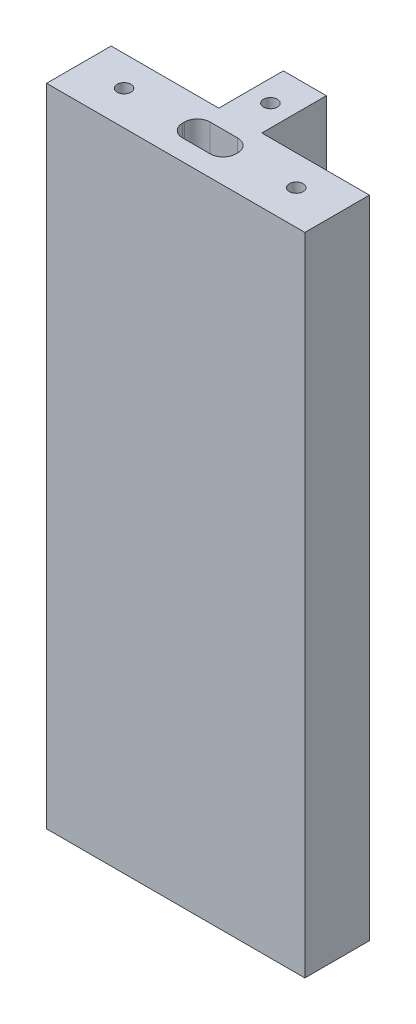
SolidWorks part; units mm, degrees
ref_plane "Front Plane" through (0, 0, 0) normal (0, 0, 1) x (1, 0, 0)
ref_plane "Top Plane" through (0, 0, 0) normal (0, 1, 0) x (1, 0, 0)
ref_plane "Right Plane" through (0, 0, 0) normal (1, 0, 0) x (0, 0, -1)
sketch "Sketch1" plane through (0, 0, 0) normal (0, 1, 0) x (1, 0, 0)
  line L0 (-15, 0) -> (15, 0)
  line L1 (15, 0) -> (15, 7.5)
  line L2 (15, 7.5) -> (2.5, 7.5)
  line L3 (2.5, 7.5) -> (2.5, 15)
  line L4 (2.5, 15) -> (-2.5, 15)
  line L5 (-2.5, 15) -> (-2.5, 7.5)
  line L6 (-2.5, 7.5) -> (-15, 7.5)
  line L7 (-15, 7.5) -> (-15, 0)
  dimension "D1" = 30
  dimension "D2" = 15
  dimension "D3" = 7.5
  dimension "D4" = 5
extrude "Boss-Extrude1" add sketch "Sketch1" along normal mid plane 75
sketch "Sketch2" plane through (0, -37.5, 0) normal (0, -1, 0) x (1, 0, 0)
  line L0 (-15, 0) -> (15, 0) construction
  line L1 (-3.1, -2.4) -> (3.1, -2.4)
  line L2 (-3.1, -2.4) -> (-3.1, -5.6)
  line L3 (-3.1, -5.6) -> (3.1, -5.6)
  line L4 (3.1, -2.4) -> (3.1, -5.6)
  point P4 (-3.1, -4)
  point P5 (0, -2.4)
  point P8 (0, 0)
  dimension "D1" = 4
  dimension "D2" = 3.2
  dimension "D3" = 6.2
extrude "Cut-Extrude1" cut sketch "Sketch2" against normal blind 6.2
fillet "Fillet1" radius 1.5 4 edges at (3.1, -34.4, -5.6) (3.1, -34.4, -2.4) (-3.1, -34.4, -5.6) (-3.1, -34.4, -2.4)
hole_wizard "M2 Tapped Hole1" positions "Sketch5" profile "Sketch6" tap size "M2" standard "DIN"
sketch "Sketch5" plane through (0, -37.5, 0) normal (0, -1, 0) x (-1, 0, 0)
  line L0 (-2.5, 15) -> (2.5, 15) construction
  line L1 (15, 0) -> (-15, 0) construction
  point P0 (10, 4)
  point P2 (0, 11)
  point P4 (-10, 4)
  point P7 (0, 0)
  dimension "D1" = 4
  dimension "D2" = 4
  dimension "D3" = 10
  dimension "D4" = 10
sketch "Sketch6" plane through (-10, -37.5, -4) normal (1, 0, 0) x (0, 0, -1)
  line L0 (0, 0) -> (0, 5.6807)
  line L1 (0, 5.6807) -> (0.8, 5.2)
  line L2 (0.8, 5.2) -> (0.8, 0)
  line L5 (0.8, 0) -> (0, 0)
  line L10 (0, 5.6807) -> (-0.8, 5.2) construction
  line L11 (0, -6.35) -> (0, 107.95) construction
  dimension "Tap Drill Dia." = 1.6
  dimension "Tap Drill Depth" = 5.2
  dimension "Drill Angle" = 118
cosmetic thread "Hole Thread1" parameters "D1"=4, "D2"=2
cosmetic thread "Hole Thread2" parameters "D1"=4, "D2"=2
cosmetic thread "Hole Thread3" parameters "D1"=4, "D2"=2
mirror "Mirror1" about plane through (0, 0, 0) normal (0, 1, 0) of "M2 Tapped Hole1", "Fillet1", "Cut-Extrude1"
